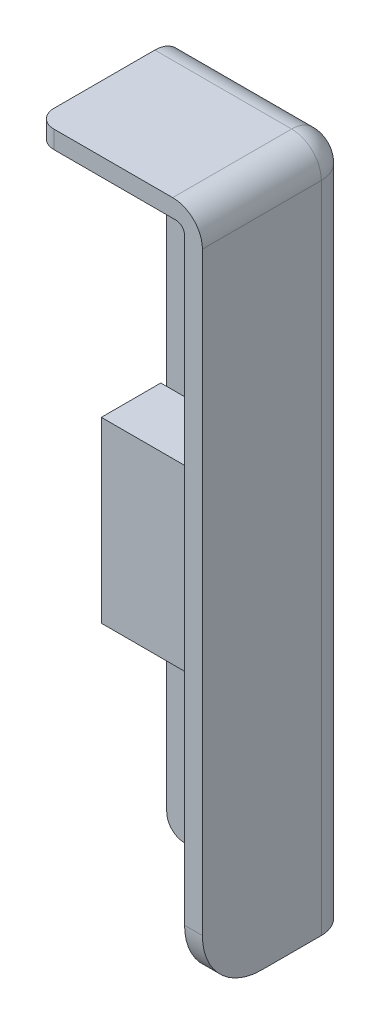
SolidWorks part; units mm, degrees
material "ABS"
ref_plane "Front" through (0, 0, 0) normal (0, 0, 1) x (1, 0, 0)
ref_plane "Top" through (0, 0, 0) normal (0, 1, 0) x (1, 0, 0)
ref_plane "Right" through (0, 0, 0) normal (1, 0, 0) x (0, 0, -1)
sketch "Sketch1" plane through (0, 0, 0) normal (1, 0, 0) x (0, 0, -1)
  line L1 (-12.5, 57.5) -> (12.5, 57.5)
  line L2 (-12.5, 57.5) -> (-12.5, -57.5)
  line L3 (-12.5, -57.5) -> (12.5, -57.5)
  line L4 (12.5, 57.5) -> (12.5, -57.5)
  line L5 (-12.5, 57.5) -> (12.5, -57.5) construction
  line L6 (-12.5, -57.5) -> (12.5, 57.5) construction
  point P0 (0, 0)
  dimension "D1" = 25
  dimension "D2" = 115
extrude "Boss-Extrude1" add sketch "Sketch1" along normal mid plane 28
sketch "Sketch3" plane through (-14, 0, 0) normal (1, 0, 0) x (0, 0, -1)
  line L1 (-12.5, -57.5) -> (9.5, -57.5)
  line L2 (-12.5, -57.5) -> (-12.5, 54.5)
  line L3 (-12.5, 54.5) -> (9.5, 54.5)
  line L4 (9.5, -57.5) -> (9.5, 54.5)
  dimension "D1" = 22
  dimension "D2" = 112
extrude "Cut-Extrude1" cut sketch "Sketch3" along normal offset from surface (25 mm away) 3 up to face at (14, 0, 0)
sketch "Sketch4" plane through (11, 0, 0) normal (-1, 0, 0) x (0, 0, 1)
  line L0 (12.5, -1.5) -> (-9.5, -1.5) construction
  line L1 (12.5, 54.5) -> (12.5, -57.5) construction
  line L2 (-9.5, -57.5) -> (-9.5, 54.5) construction
  line L4 (-3.5, 13.5) -> (6.5, 13.5)
  line L5 (-3.5, 13.5) -> (-3.5, -16.5)
  line L6 (-3.5, -16.5) -> (6.5, -16.5)
  line L7 (6.5, 13.5) -> (6.5, -16.5)
  line L8 (-3.5, 13.5) -> (6.5, -16.5) construction
  line L9 (-3.5, -16.5) -> (6.5, 13.5) construction
  point P6 (1.5, -1.5)
  dimension "D1" = 30
  dimension "D2" = 10
extrude "Boss-Extrude2" add sketch "Sketch4" along normal blind 20
hole_wizard "#2 Clearance Hole1" positions "Sketch5" profile "Sketch6" hole size "#2" standard "ANSI Inch"
sketch "Sketch5" plane through (-9, 0, 0) normal (-1, 0, 0) x (0, 0, 1)
  line L0 (1.5, 13.5) -> (1.5, -16.5) construction
  line L1 (6.5, 13.5) -> (-3.5, 13.5) construction
  line L2 (-3.5, -16.5) -> (6.5, -16.5) construction
  line L4 (-3.5, -1.5) -> (6.5, -1.5) construction
  line L5 (-3.5, 13.5) -> (-3.5, -16.5) construction
  line L6 (6.5, -16.5) -> (6.5, 13.5) construction
  point P0 (1.5, 8.5)
  point P2 (1.5, -11.5)
  dimension "D1" = 10
  dimension "D2" = 10
sketch "Sketch6" plane through (-9, 8.5, 1.5) normal (0, 1, 0) x (0, 0, 1)
  line L0 (0, 0) -> (0, 7.0292)
  line L1 (0, 7.0292) -> (1.1303, 6.35)
  line L2 (1.1303, 6.35) -> (1.1303, 0)
  line L5 (1.1303, 0) -> (0, 0)
  line L10 (0, 7.0292) -> (-1.1303, 6.35) construction
  line L11 (0, -6.35) -> (0, 107.95) construction
  dimension "Hole Dia." = 2.2606
  dimension "Hole Depth" = 6.35
  dimension "Drill Angle" = 118
fillet "Fillet1" radius 1.5 3 edges at (11, -1.5, -9.5) (-1.5, 54.5, -9.5) (11, 54.5, 1.5)
fillet "Fillet3" radius 5 3 edges at (0, 57.5, -12.5) (14, 57.5, 0) (14, 0, -12.5)
fillet "Fillet4" radius 10 1 edges at (12.5, -57.5, 12.5)
fillet "Fillet5" radius 3 2 edges at (-14, -57.5, -11) (-14, 56, 12.5)
fillet "Fillet6" radius 3 4 edges at (11, 13.5, 1.5) (11, -1.5, -3.5) (11, -16.5, 1.5) (11, -1.5, 6.5)
sketch "Sketch7" plane through (14, 0, 0) normal (1, 0, 0) x (0, 0, -1)
  circle A0 centre (-1.5006, -43.0001) radius 3.7 construction
  arc A1 (-3.6164, -46.0355) -> (-4.1645, -40.4322) centre (-1.5006, -43.0001) ccw construction
  circle A2 centre (-1.5006, -43.0001) radius 2.7
  dimension "D1" = 1
extrude "Boss-Extrude3" add sketch "Sketch7" against normal blind 8
fillet "Fillet7" radius 1 2 edges at (11, -43.0001, -1.1994) (6, -43.0001, -1.1994)
